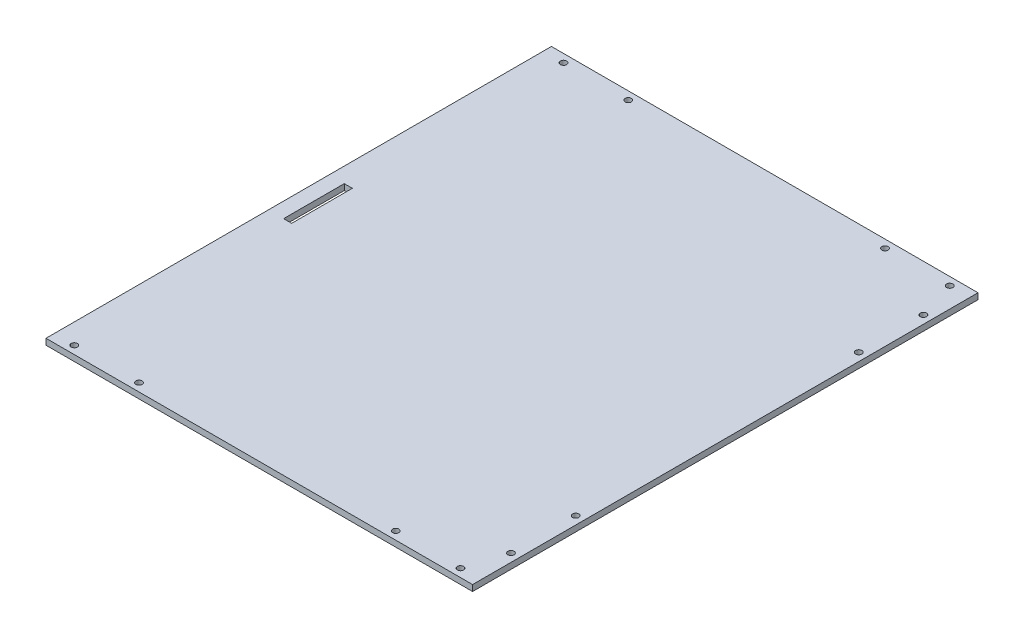
SolidWorks part; units mm, degrees
ref_plane "Front Plane" through (0, 0, 0) normal (0, 0, 1) x (1, 0, 0)
ref_plane "Top Plane" through (0, 0, 0) normal (0, 1, 0) x (1, 0, 0)
ref_plane "Right Plane" through (0, 0, 0) normal (1, 0, 0) x (0, 0, -1)
sketch "Sketch1" plane through (0, 0, 0) normal (0, 1, 0) x (1, 0, 0)
  line L0 (0, 125) -> (211, 125) construction
  line L1 (0, 0) -> (211, 0)
  line L2 (0, 0) -> (0, 250)
  line L3 (0, 250) -> (211, 250)
  line L4 (211, 0) -> (211, 250)
  line L5 (105.5, 250) -> (105.5, 0) construction
  line L6 (9.525, 140) -> (9.525, 110) construction
  line L7 (7.525, 140) -> (11.525, 140)
  line L8 (7.525, 140) -> (7.525, 110)
  line L9 (7.525, 110) -> (11.525, 110)
  line L10 (11.525, 140) -> (11.525, 110)
  circle A0 centre (10, 4) radius 1.55
  circle A4 centre (42, 4) radius 1.55
  circle A5 centre (42, 246) radius 1.55
  circle A6 centre (10, 246) radius 1.55
  circle A7 centre (169, 4) radius 1.55
  circle A8 centre (201, 4) radius 1.55
  circle A9 centre (169, 246) radius 1.55
  circle A10 centre (201, 246) radius 1.55
  circle A11 centre (207, 23) radius 1.55
  circle A12 centre (207, 55) radius 1.55
  circle A13 centre (207, 227) radius 1.55
  circle A14 centre (207, 195) radius 1.55
  point P39 (9.525, 125)
  dimension "D3" = 3.1
  dimension "D8" = 3.1
  dimension "D1" = 250
  dimension "D2" = 211
  dimension "D4" = 4
  dimension "D5" = 10
  dimension "D6" = 32
  dimension "D7" = 23
  dimension "D9" = 4
  dimension "D10" = 32
  dimension "D11" = 9.525
  dimension "D12" = 4
  dimension "D13" = 30
extrude "Boss-Extrude1" add sketch "Sketch1" along normal blind 3
equation "\"cf_tube_outer_diameter\"= 25mm"
equation "\"cf_tube_inner_diameter\"= 21mm"
equation "\"mid_plate_mid_to_top\"= 100mm"
equation "\"mid_plate_mid_to_bottom\"= 30mm"
equation "\"mid_plate_horizontal_spacing\"= 250mm"
equation "\"cf_plate_thickness\"= 3mm"
equation "\"mid_tube_length\"= 500mm"
equation "\"mid_plate_bottom_width\"= 180mm"
equation "\"D1@Sketch1\"=\"mid_plate_horizontal_spacing\""
equation "\"mid_support_plate_distance\"= 250mm"
equation "\"D1@Boss-Extrude1\"=\"cf_plate_thickness\""
equation "\"nut_strip_2_hole_distance\"= 7mm"
equation "\"nut_strip_hole_diameter\"= 2.5mm"
equation "\"nut_strip_hole_to_edge_distance\"= 2.5mm"
equation "\"M3_screw_hole_diameter\"= 3.1mm"
equation "\"D3@Sketch1\"=\"M3_screw_hole_diameter\""
equation "\"D8@Sketch1\"=\"M3_screw_hole_diameter\""
